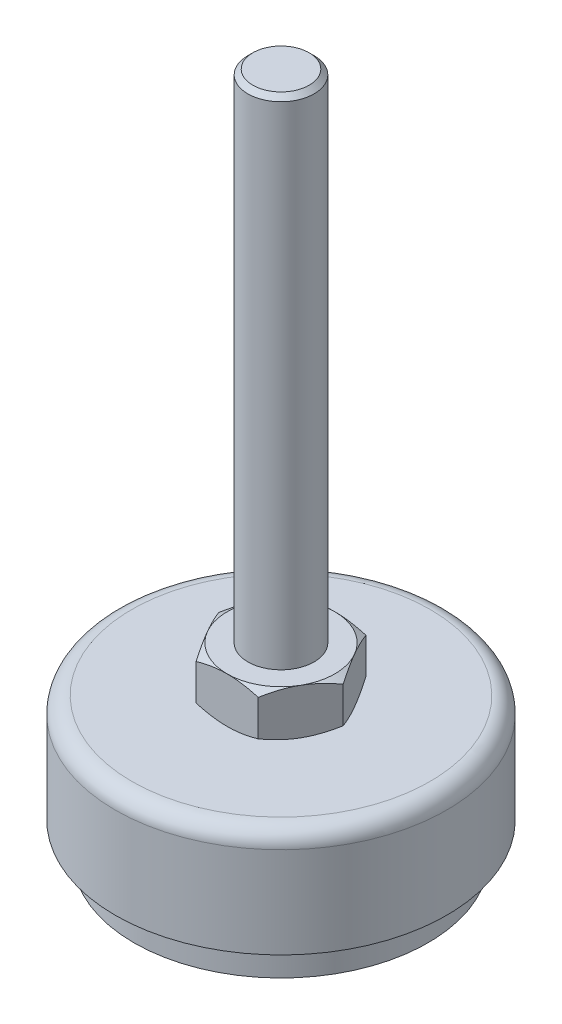
SolidWorks part; units mm, degrees
ref_plane "Front Plane" through (0, 0, 0) normal (0, 0, 1) x (1, 0, 0)
ref_plane "Top Plane" through (0, 0, 0) normal (0, 1, 0) x (1, 0, 0)
ref_plane "Right Plane" through (0, 0, 0) normal (1, 0, 0) x (0, 0, -1)
ref_axis "Axis_X" through (-22, 0, 0) along (1, 0, 0)
ref_axis "Axis_Y" through (0, 86.625, 0) along (0, -1, 0)
ref_axis "Axis_Z" through (0, 0, -22) along (0, 0, 1)
sketch "Sketch1" plane through (0, 0, 0) normal (0, 0, 1) x (1, 0, 0)
  line L0 (0, 0) -> (-17.75, 0)
  line L1 (-17.75, 0) -> (-17.75, 4)
  line L2 (-20, 4) -> (-17.75, 4)
  line L3 (-4, 81.9) -> (-4, 82.5) construction
  line L4 (-20, 4) -> (-20, 15)
  line L5 (-4, 82.5) -> (-3.4, 82.5) construction
  line L6 (-18, 17) -> (-4, 17)
  line L7 (-4, 17) -> (-4, 81.9)
  line L8 (-4, 81.9) -> (-3.4, 82.5)
  line L9 (-3.4, 82.5) -> (0, 82.5)
  line L10 (0, 82.5) -> (0, 0) construction
  line L11 (0, 86.625) -> (0, -4.125) construction
  line L12 (-22, 0) -> (22, 0) construction
  line L13 (0, 82.5) -> (0, 0)
  arc A0 (-18, 17) -> (-20, 15) centre (-18, 15) ccw
  dimension "FIX_1" = 2
  dimension "D_s" = 35.5
  dimension "FIX_2" = 4
  dimension "E" = 17
  dimension "M" = 8
  dimension "MSM_1" = 0.6
  dimension "L" = 82.5
  dimension "D" = 40
revolve "Revolve1" add sketch "Sketch1" angle 360 about axis through (0, 86.625, 0) along (0, -1, 0) region at (-8.875, 0.8489, 0)
cosmetic thread "Thread1" parameters "ATD_1"=6.647
sketch "Sketch2" plane through (0, 82.5, 0) normal (0, 1, 0) x (0, 0, -1)
  line L1 (6.5, -3.7528) -> (6.5, 3.7528)
  line L2 (6.5, 3.7528) -> (0, 7.5056)
  line L3 (0, 7.5056) -> (-6.5, 3.7528)
  line L4 (-6.5, 3.7528) -> (-6.5, -3.7528)
  line L5 (-6.5, -3.7528) -> (0, -7.5056)
  line L6 (0, -7.5056) -> (6.5, -3.7528)
  line L7 (0, 0) -> (0, 7.5056) construction
  line L8 (0, -7.5056) -> (0, -6.5) construction
  circle A0 centre (0, 0) radius 6.5 construction
  dimension "B" = 13
extrude "Boss-Extrude1" add sketch "Sketch2" against normal blind 5.5 from offset 60 offset against normal yes
sketch "Sketch3" plane through (0, 0, 0) normal (0, 0, 1) x (1, 0, 0)
  line L0 (7.5056, 22.5) -> (6.5, 22.5)
  line L2 (6.5, 22.5) -> (7.5056, 21.9194)
  line L3 (7.5056, 17) -> (7.5056, 22.5) construction
  line L4 (7.5056, 21.9194) -> (7.5056, 22.5)
  line L5 (7.5056, 17) -> (6.5, 17)
  line L6 (6.5, 17) -> (7.5056, 17.5806)
  line L7 (7.5056, 17.5806) -> (7.5056, 17)
  dimension "FIX_4" = 30
revolve "Cut-Revolve1" cut sketch "Sketch3" angle 360 about axis through (0, 86.625, 0) along (0, -1, 0)
equation "\"Factor\"= 1.082532"
